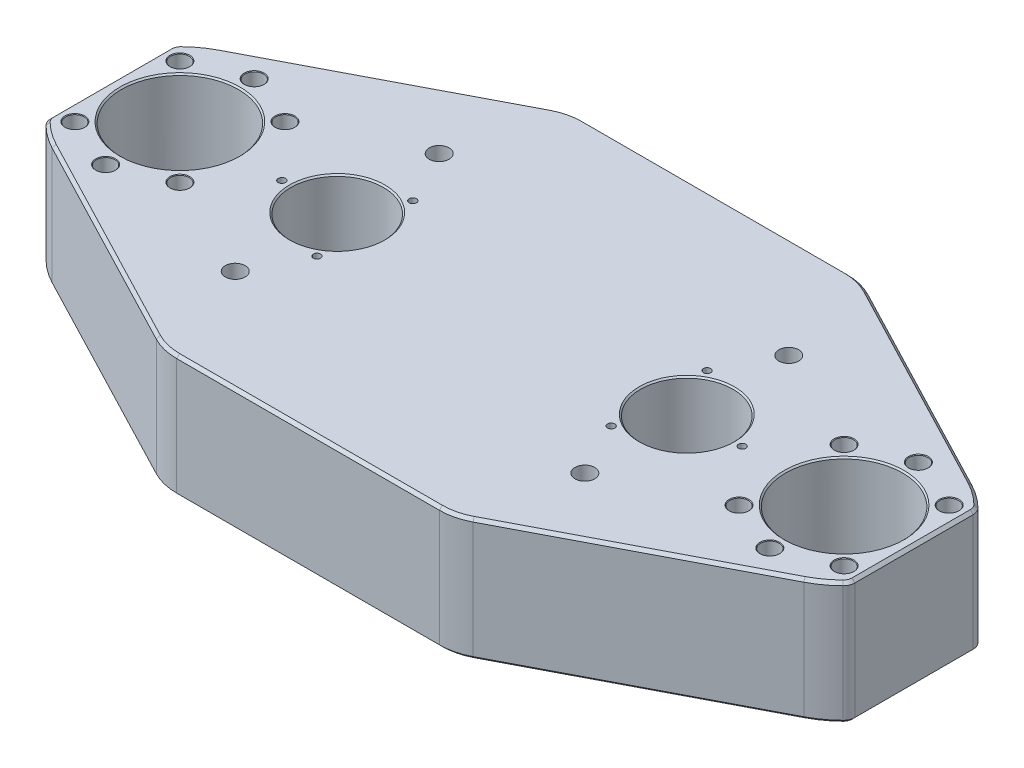
SolidWorks part; units mm, degrees
material "6061-T6 Aluminum"
ref_plane "Front Plane" through (0, 0, 0) normal (0, 0, 1) x (1, 0, 0)
ref_plane "Top Plane" through (0, 0, 0) normal (0, 1, 0) x (1, 0, 0)
ref_plane "Right Plane" through (0, 0, 0) normal (1, 0, 0) x (0, 0, -1)
sketch "Sketch1" plane through (0, 0, 0) normal (0, 1, 0) x (1, 0, 0)
  line L0 (114, 0) -> (0, 0) construction
  line L1 (0, 0) -> (-114, 0) construction
  line L2 (-60, 0) -> (0, 0) construction
  line L3 (0, 0) -> (60, 0) construction
  line L18 (0, 70) -> (0, 0) construction
  line L19 (0, 0) -> (0, -70) construction
  line L20 (-129.0194, 28.8213) -> (-54.3441, 67.7362)
  line L21 (-45.1014, 70) -> (45.1014, 70)
  line L22 (54.3441, 67.7362) -> (129.0194, 28.8213)
  line L23 (-129.0194, -28.8213) -> (-54.3441, -67.7362)
  line L24 (-45.1014, -70) -> (45.1014, -70)
  line L25 (54.3441, -67.7362) -> (129.0194, -28.8213)
  line L26 (-138, 20.3039) -> (-138, -20.3039)
  line L27 (138, 20.3039) -> (138, -20.3039)
  line L28 (-138, 0) -> (-114, 0) construction
  line L29 (114, 0) -> (138, 0) construction
  circle A0 centre (-114, 0) radius 20.1
  circle A1 centre (114, 0) radius 20.1
  circle A2 centre (-60, 0) radius 15.875
  circle A3 centre (60, 0) radius 15.875
  arc A6 (-54.3441, -67.7362) -> (-45.1014, -70) centre (-45.1014, -50) ccw
  arc A7 (45.1014, -70) -> (54.3441, -67.7362) centre (45.1014, -50) ccw
  arc A8 (-129.0194, 28.8213) -> (-136.807, 23.1536) centre (-114, 0) ccw
  arc A9 (129.0194, -28.8213) -> (136.807, -23.1536) centre (114, 0) ccw
  arc A10 (45.1014, 70) -> (54.3441, 67.7362) centre (45.1014, 50) cw
  arc A11 (-54.3441, 67.7362) -> (-45.1014, 70) centre (-45.1014, 50) cw
  arc A12 (-136.807, -23.1536) -> (-129.0194, -28.8213) centre (-114, 0) ccw
  arc A13 (136.807, 23.1536) -> (129.0194, 28.8213) centre (114, 0) ccw
  arc A14 (136.807, -23.1536) -> (138, -20.3039) centre (134, -20.3039) ccw
  arc A15 (136.807, 23.1536) -> (138, 20.3039) centre (134, 20.3039) cw
  arc A16 (-136.807, -23.1536) -> (-138, -20.3039) centre (-134, -20.3039) cw
  arc A17 (-136.807, 23.1536) -> (-138, 20.3039) centre (-134, 20.3039) ccw
  point P23 (138.7644, 40.8255)
  point P30 (-50, -70)
  point P36 (50, 70)
  point P39 (-50, 70)
  point P46 (0, 0)
  dimension "D1" = 40.2
  dimension "D3" = 120
  dimension "D7" = 31.75
  dimension "D8" = 20
  dimension "D6" = 32.5
  dimension "D9" = 276
  dimension "D10" = 4
  dimension "D11" = 32.5
  dimension "D2" = 228
  dimension "D4" = 140
  dimension "D5" = 100
extrude "Boss-Extrude1" add sketch "Sketch1" along normal mid plane 42
sketch "Sketch7" plane through (0, -21, 0) normal (0, -1, 0) x (1, 0, 0)
  circle A0 centre (95.9688, 18.0312) radius 3.3 construction
  circle A1 centre (114, 25.5) radius 3.3 construction
  circle A2 centre (132.0312, 18.0312) radius 3.3 construction
  circle A3 centre (132.0312, -18.0312) radius 3.3 construction
  circle A4 centre (114, -25.5) radius 3.3 construction
  circle A5 centre (95.9688, -18.0312) radius 3.3 construction
  circle A6 centre (95.9688, 18.0312) radius 3.3
  circle A7 centre (114, 25.5) radius 3.3
  circle A8 centre (132.0312, 18.0312) radius 3.3
  circle A9 centre (132.0312, -18.0312) radius 3.3
  circle A10 centre (114, -25.5) radius 3.3
  circle A11 centre (95.9688, -18.0312) radius 3.3
hole_wizard "M6 Clearance Hole1" positions "Sketch8" profile "Sketch9" hole size "M6" standard "ANSI Metric" end condition through all
sketch "Sketch8" plane through (0, -21, 0) normal (0, -1, 0) x (-1, 0, 0)
  point P0 (-95.9688, -18.0312)
  point P3 (-114, -25.5)
  point P6 (-132.0312, -18.0312)
  point P9 (-132.0312, 18.0312)
  point P12 (-114, 25.5)
  point P15 (-95.9688, 18.0312)
sketch "Sketch9" plane through (95.9688, -21, 18.0312) normal (1, 0, 0) x (0, 0, -1)
  line L0 (0, 0) -> (0, 42)
  line L1 (0, 42) -> (3.2, 42)
  line L2 (3.2, 42) -> (3.2, 0)
  line L5 (3.2, 0) -> (0, 0)
  line L11 (0, -6.35) -> (0, 107.95) construction
  dimension "Thru Hole Dia." = 6.4
  dimension "Thru Hole Depth" = 42
mirror "Mirror5" about plane through (0, 0, 0) normal (1, 0, 0) of "M6 Clearance Hole1"
chamfer "Chamfer2" distance 0.5 angle 45 4 edges at (114, 21, 20.1) (114, -21, 20.1) (-114, -21, 20.1) (-114, 21, 20.1)
chamfer "Chamfer3" [suppressed] distance 1 angle 45
chamfer "Chamfer5" distance 1 angle 45 40 edges at (91.6818, -21, -48.2787) (-91.6818, -21, -48.2787) (49.8594, -21, -69.4258) (-49.8594, -21, -69.4258) (0, -21, -70) (-133.1243, -21, -26.2776) (133.1243, -21, 26.2776) (-91.6818, -21, 48.2787) (91.6818, -21, 48.2787) (-49.8594, -21, 69.4258) (49.8594, -21, 69.4258) (0, -21, 70) (91.6818, 21, -48.2787) (-91.6818, 21, -48.2787) (49.8594, 21, -69.4258) (-49.8594, 21, -69.4258) (0, 21, -70) (-133.1243, 21, -26.2776) (133.1243, 21, 26.2776) (-91.6818, 21, 48.2787) (91.6818, 21, 48.2787) (-49.8594, 21, 69.4258) (49.8594, 21, 69.4258) (0, 21, 70) (133.1243, -21, -26.2776) (-133.1243, -21, 26.2776) (133.1243, 21, -26.2776) (-133.1243, 21, 26.2776) (-137.6897, -21, -21.8486) (137.6897, -21, -21.8486) (-138, -21, 0) (138, -21, 0) (-137.6897, -21, 21.8486) (137.6897, -21, 21.8486) (-137.6897, 21, -21.8486) (137.6897, 21, -21.8486) (-138, 21, 0) (138, 21, 0) (-137.6897, 21, 21.8486) (137.6897, 21, 21.8486)
chamfer "Chamfer6" distance 0.5 angle 45 4 edges at (60, -21, 15.875) (60, 21, 15.875) (-60, -21, 15.875) (-60, 21, 15.875)
sketch "Sketch10" plane through (0, 21, 0) normal (0, 1, 0) x (1, 0, 0)
  line L0 (50.5, -16.4545) -> (50.5, 16.4545) construction
  line L1 (50.5, 16.4545) -> (79, 0) construction
  line L2 (79, 0) -> (50.5, -16.4545) construction
  circle A3 centre (50.5, -16.4545) radius 1.7
  circle A4 centre (50.5, 16.4545) radius 1.7
  circle A5 centre (79, 0) radius 1.7
  circle A6 centre (60, 0) radius 19 construction
  dimension "D1" = 38
hole_wizard "M3x0.5 Tapped Hole1" positions "Sketch11" profile "Sketch13" tap size "M3x0.5" standard "ANSI Metric"
sketch "Sketch11" plane through (0, 21, 0) normal (0, 1, 0) x (1, 0, 0)
  point P0 (79, 0)
  point P3 (50.5, -16.4545)
  point P6 (50.5, 16.4545)
sketch "Sketch13" plane through (79, 21, 0) normal (1, 0, 0) x (0, 0, 1)
  line L0 (0, 0) -> (0, 8.2511)
  line L1 (0, 8.2511) -> (1.25, 7.5)
  line L2 (1.25, 7.5) -> (1.25, 0)
  line L5 (1.25, 0) -> (0, 0)
  line L10 (0, 8.2511) -> (-1.25, 7.5) construction
  line L11 (0, -6.35) -> (0, 107.95) construction
  dimension "Tap Drill Dia." = 2.5
  dimension "Tap Drill Depth" = 7.5
  dimension "Drill Angle" = 118
cosmetic thread "Hole Thread9" parameters "D1"=6, "D2"=3
cosmetic thread "Hole Thread13" parameters "D1"=6, "D2"=3
cosmetic thread "Hole Thread14" parameters "D1"=6, "D2"=3
mirror "Mirror6" about plane through (0, 0, 0) normal (1, 0, 0) of "M3x0.5 Tapped Hole1"
mirror "Mirror7" about plane through (0, 0, 0) normal (0, 1, 0) of "Mirror6"
sketch "Sketch14" plane through (0, -21, 0) normal (0, -1, 0) x (1, 0, 0)
  line L0 (-60, 0) -> (-60, -35) construction
  circle A1 centre (-60, -35) radius 3.25
  dimension "D1" = 35
chamfer "Chamfer9" distance 0.2 angle 45 24 edges at (-132.0312, -21, -21.2312) (-132.0312, 21, -21.2312) (-114, -21, -28.7) (-114, 21, -28.7) (-95.9688, -21, -21.2312) (-95.9688, 21, -21.2312) (-95.9688, -21, 14.8312) (-95.9688, 21, 14.8312) (-114, -21, 22.3) (-114, 21, 22.3) (-132.0312, -21, 14.8312) (-132.0312, 21, 14.8312) (132.0312, -21, 14.8312) (132.0312, 21, 14.8312) (114, -21, 22.3) (114, 21, 22.3) (95.9688, -21, 14.8312) (95.9688, 21, 14.8312) (95.9688, -21, -21.2312) (95.9688, 21, -21.2312) (132.0312, -21, -21.2312) (132.0312, 21, -21.2312) (114, -21, -28.7) (114, 21, -28.7)
sketch "Sketch15" plane through (0, -21, 0) normal (0, -1, 0) x (1, 0, 0)
  circle A1 centre (-60, -35) radius 3.05
  point P0 (-60, -35)
  point P6 (-60, -35)
hole_wizard "M8x1.25 Tapped Hole1" positions "Sketch15" profile "Sketch16" tap size "M8x1.25" standard "ANSI Metric" end condition through all
cosmetic thread "Hole Thread15" parameters "D2"=8
sketch "Sketch16" plane through (-60, -21, -35) normal (1, 0, 0) x (0, 0, -1)
  line L0 (0, 0) -> (0, 42)
  line L1 (0, 42) -> (3.4, 42)
  line L2 (3.4, 42) -> (3.4, 0)
  line L5 (3.4, 0) -> (0, 0)
  line L11 (0, -6.35) -> (0, 107.95) construction
  dimension "Thru Tap Drill Dia." = 6.8
  dimension "Thru Tap Drill Depth" = 42
mirror "Mirror8" about plane through (0, 0, 0) normal (0, 0, 1) of "M8x1.25 Tapped Hole1"
mirror "Mirror9" about plane through (0, 0, 0) normal (1, 0, 0) of "Mirror8"
